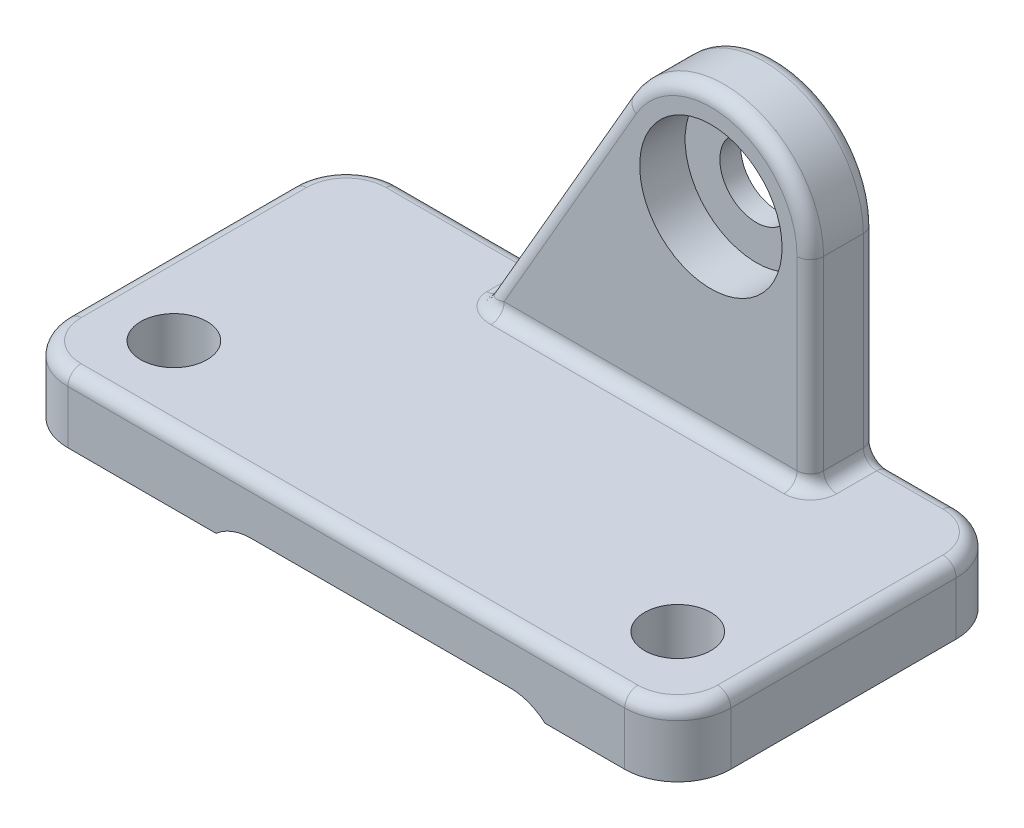
SolidWorks part; units mm, degrees
ref_plane "Front Plane" through (0, 0, 0) normal (0, 0, 1) x (1, 0, 0)
ref_plane "Top Plane" through (0, 0, 0) normal (0, 1, 0) x (1, 0, 0)
ref_plane "Right Plane" through (0, 0, 0) normal (1, 0, 0) x (0, 0, -1)
sketch "Sketch1" plane through (0, 0, 0) normal (0, 1, 0) x (1, 0, 0)
  line L1 (0, 0) -> (100, 0)
  line L2 (0, 0) -> (0, 50)
  line L3 (0, 50) -> (100, 50)
  line L4 (100, 0) -> (100, 50)
  dimension "D1" = 100
  dimension "D2" = 50
extrude "Base" add sketch "Sketch1" along normal blind 10 contours L3 L4 L1 L2
sketch "Sketch4" plane through (0, 0, -50) normal (0, 0, -1) x (-1, 0, 0)
  line L0 (-80, 10) -> (-80, 40)
  line L1 (0, 10) -> (-100, 10) construction
  line L2 (-52.0096, 47.5) -> (-30.359, 10)
  line L3 (-30.359, 10) -> (-80, 10)
  arc A0 (-80, 40) -> (-52.0096, 47.5) centre (-65, 40) cw
  dimension "D4" = 15
  dimension "D1" = 20
  dimension "D2" = 30
  dimension "D3" = 60
extrude "TopBoss" add sketch "Sketch4" against normal blind 10 contours L0 A0 L2 L3
sketch "Sketch6" plane through (0, 0, 0) normal (0, 0, 1) x (1, 0, 0)
  line L0 (0, 0) -> (100, 0) construction
  line L1 (30.359, 0) -> (80, 0)
  line L2 (30.359, 0) -> (30.359, 2)
  line L3 (30.359, 2) -> (80, 2)
  line L4 (80, 0) -> (80, 2)
  line L8 (80, 10) -> (80, 40) construction
  point P10 (0, 0)
  dimension "D1" = 2
extrude "BottomCut" cut sketch "Sketch6" against normal blind 50
hole_wizard "CBORE for M10 Hex Head Bolt1" positions "Sketch9" profile "Sketch10" counterbore size "M10" standard "ANSI Metric" end condition through all
sketch "Sketch9" plane through (0, 0, -40) normal (0, 0, 1) x (1, 0, 0)
  point P0 (65, 40)
sketch "Sketch10" plane through (65, 40, -40) normal (1, 0, 0) x (0, -1, 0)
  line L0 (0, 0) -> (0, 10)
  line L1 (0, 10) -> (5.5, 10)
  line L3 (5.5, 10) -> (5.5, 6.85)
  line L4 (5.5, 6.85) -> (10.74, 6.85)
  line L5 (10.74, 6.85) -> (10.74, 0)
  line L7 (10.74, 0) -> (0, 0)
  line L11 (0, -6.35) -> (0, 107.95) construction
  dimension "Thru Hole Dia." = 11
  dimension "Thru Hole Depth" = 10
  dimension "C'Bore Dia." = 21.48
  dimension "C'Bore Depth" = 6.85
hole_wizard "Ø10.0 (10) Diameter Hole1" positions "Sketch12" profile "Sketch13" hole size "Ø10.0" standard "ANSI Metric" end condition through all
sketch "Sketch12" plane through (0, 10, 0) normal (0, 1, 0) x (1, 0, 0)
  line L0 (0, 0) -> (100, 0) construction
  line L1 (0, 0) -> (0, 50) construction
  line L2 (100, 0) -> (100, 50) construction
  point P0 (12, 12)
  point P2 (88, 12)
  point P19 (87.6163, 9.3413)
  point P24 (76.1947, 0.9899)
  point P25 (0, 0)
  dimension "D1" = 12
  dimension "D2" = 12
  dimension "D3" = 12
  dimension "D4" = 12
sketch "Sketch13" plane through (12, 10, -12) normal (1, 0, 0) x (0, 0, 1)
  line L0 (0, 0) -> (0, 10)
  line L1 (0, 10) -> (5, 10)
  line L2 (5, 10) -> (5, 0)
  line L5 (5, 0) -> (0, 0)
  line L11 (0, -6.35) -> (0, 107.95) construction
  dimension "Thru Hole Dia." = 10
  dimension "Thru Hole Depth" = 10
fillet "Fillet1" radius 8 6 edges at (80, 2, -25) (30.359, 2, -25) (0, 5, -50) (100, 5, -50) (0, 5, 0) (100, 5, 0)
fillet "Fillet2" radius 2 18 edges at (41.1843, 28.75, -40) (68.8823, 54.4889, -40) (41.1843, 28.75, -50) (68.8823, 54.4889, -50) (80, 25, -40) (80, 25, -50) (2.3431, 10, -2.3431) (0, 10, -25) (50, 10, 0) (2.3431, 10, -47.6569) (97.6569, 10, -2.3431) (19.1795, 10, -50) (100, 10, -25) (30.359, 10, -45) (97.6569, 10, -47.6569) (55.1795, 10, -40) (86, 10, -50) (80, 10, -45)
